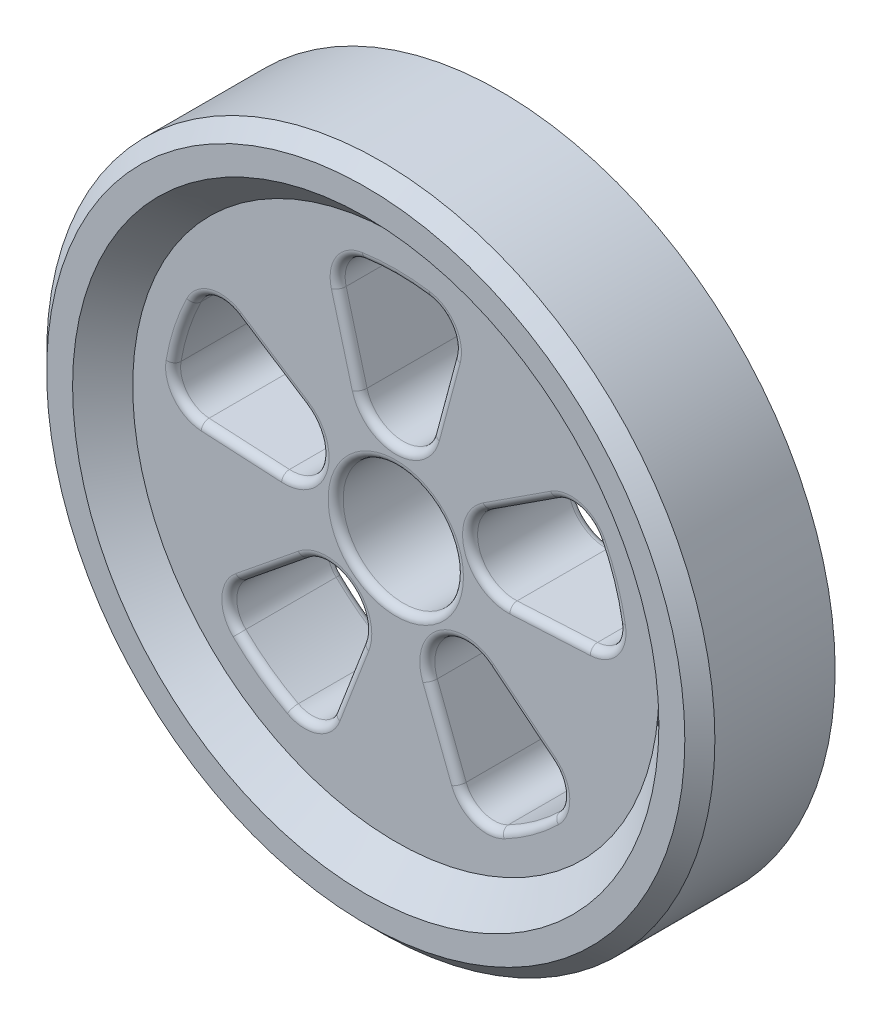
SolidWorks part; units mm, degrees
ref_plane "Front Plane" through (0, 0, 0) normal (0, 0, 1) x (1, 0, 0)
ref_plane "Top Plane" through (0, 0, 0) normal (0, 1, 0) x (1, 0, 0)
ref_plane "Right Plane" through (0, 0, 0) normal (1, 0, 0) x (0, 0, -1)
sketch "Sketch1" plane through (0, 0, 0) normal (0, 0, 1) x (1, 0, 0)
  line L0 (0, 0) -> (0, 10) construction
  line L1 (0, 0) -> (-7.0711, 7.0711) construction
  line L2 (2.4148, 7.1746) -> (3.8008, 12.3473)
  line L3 (-2.4148, 7.1746) -> (-3.8008, 12.3473)
  line L4 (6.0772, 4.5137) -> (10.5685, 7.4303)
  line L5 (7.5696, -0.0796) -> (12.9175, 0.2007)
  line L6 (6.1707, -4.385) -> (10.3325, -7.7551)
  line L7 (2.2635, -7.2237) -> (4.1826, -12.2233)
  line L8 (-2.2635, -7.2237) -> (-4.1826, -12.2233)
  line L9 (-6.1707, -4.385) -> (-10.3325, -7.7551)
  line L10 (-7.5696, -0.0796) -> (-12.9175, 0.2007)
  line L11 (-6.0772, 4.5137) -> (-10.5685, 7.4303)
  circle A1 centre (0, 0) radius 4
  circle A2 centre (0, 0) radius 10 construction
  circle A3 centre (0, 0) radius 22.225
  arc A4 (2.4148, 7.1746) -> (-2.4148, 7.1746) centre (0, 7.8216) cw
  arc A5 (52.7898, 163.2337) -> (51.4473, 165.6465) centre (50.8541, 163.7365) ccw
  arc A6 (2.1565, 14.8442) -> (-2.1565, 14.8442) centre (0, 0) ccw
  arc A7 (3.8008, 12.3473) -> (2.1565, 14.8442) centre (1.869, 12.8649) ccw
  arc A8 (-3.8008, 12.3473) -> (-2.1565, 14.8442) centre (-1.869, 12.8649) cw
  arc A9 (14.784, 2.5361) -> (13.4512, 6.6381) centre (0, 0) ccw
  arc A10 (12.9175, 0.2007) -> (14.784, 2.5361) centre (12.8128, 2.198) ccw
  arc A11 (10.5685, 7.4303) -> (13.4512, 6.6381) centre (11.6577, 5.753) cw
  arc A12 (7.5696, -0.0796) -> (6.0772, 4.5137) centre (7.4388, 2.417) cw
  arc A13 (6.9805, -13.2768) -> (10.4699, -10.7416) centre (0, 0) ccw
  arc A14 (4.1826, -12.2233) -> (6.9805, -13.2768) centre (6.0498, -11.5065) ccw
  arc A15 (10.3325, -7.7551) -> (10.4699, -10.7416) centre (9.0739, -9.3094) cw
  arc A16 (2.2635, -7.2237) -> (6.1707, -4.385) centre (4.5974, -6.3278) cw
  arc A17 (-10.4699, -10.7416) -> (-6.9805, -13.2768) centre (0, 0) ccw
  arc A18 (-10.3325, -7.7551) -> (-10.4699, -10.7416) centre (-9.0739, -9.3094) ccw
  arc A19 (-4.1826, -12.2233) -> (-6.9805, -13.2768) centre (-6.0498, -11.5065) cw
  arc A20 (-6.1707, -4.385) -> (-2.2635, -7.2237) centre (-4.5974, -6.3278) cw
  arc A21 (-13.4512, 6.6381) -> (-14.784, 2.5361) centre (0, 0) ccw
  arc A22 (-10.5685, 7.4303) -> (-13.4512, 6.6381) centre (-11.6577, 5.753) ccw
  arc A23 (-12.9175, 0.2007) -> (-14.784, 2.5361) centre (-12.8128, 2.198) cw
  arc A24 (-6.0772, 4.5137) -> (-7.5696, -0.0796) centre (-7.4388, 2.417) cw
  point P14 (53.2668, 165.0703)
  point P18 (4.3397, 14.3585)
  point P22 (-4.3397, 14.3585)
  point P61 (0, 0)
  dimension "D1" = 20
  dimension "D2" = 44.45
  dimension "D3" = 8
  dimension "D5" = 2
  dimension "D6" = 5
  dimension "D8" = 2.5
  dimension "D9" = 15
  dimension "D4" = 45
  dimension "D10" = 15
extrude "Boss-Extrude1" add sketch "Sketch1" along normal mid plane 9 contours A3 A1 L3 A8 A6 A7 L2 A4 L5 A12 L4 A11 A9 A10 L7 A16 L6 A15 A13 A14 L9 A20 L8 A19 A17 A18 L11 A24 L10 A23 A21 A22 region at (-21.5964, 0, 0)
sketch "Sketch2" plane through (0, 0, 4.5) normal (0, 0, 1) x (1, 0, 0)
  circle A0 centre (0, 0) radius 17.5
  dimension "D1" = 35
extrude "Cut-Extrude1" cut sketch "Sketch2" against normal blind 2
chamfer "Chamfer1" distance 2 angle 45 1 edges at (17.5, 0, 4.5)
chamfer "Chamfer2" distance 1 angle 45 1 edges at (22.225, 0, 4.5)
fillet "Fillet4" radius 0.5 62 edges at (-5.0612, 1.6445, -4.5) (-10.2436, 0.0606, -4.5) (-14.3752, 0.9493, -4.5) (-14.2658, 4.6353, -4.5) (-12.1877, 7.6815, -4.5) (-8.3228, 5.972, -4.5) (-3.128, -4.3053, -4.5) (-3.223, -9.7235, -4.5) (-5.345, -13.3782, -4.5) (-8.8168, -12.1353, -4.5) (-11.0718, -9.2175, -4.5) (-8.2516, -6.07, -4.5) (3.128, -4.3053, -4.5) (8.2516, -6.07, -4.5) (11.0718, -9.2175, -4.5) (8.8168, -12.1353, -4.5) (5.345, -13.3782, -4.5) (3.223, -9.7235, -4.5) (5.0612, 1.6445, -4.5) (8.3228, 5.972, -4.5) (12.1877, 7.6815, -4.5) (14.2658, 4.6353, -4.5) (10.2436, 0.0606, -4.5) (-3.5393, 13.9649, -4.5) (0, 15, -4.5) (3.5393, 13.9649, -4.5) (3.1078, 9.7609, -4.5) (0, 5.3216, -4.5) (-3.1078, 9.7609, -4.5) (4, 0, -4.5) (14.3752, 0.9493, -4.5) (0, 5.3216, 2.5) (3.1078, 9.7609, 2.5) (3.5393, 13.9649, 2.5) (0, 15, 2.5) (-3.5393, 13.9649, 2.5) (-3.1078, 9.7609, 2.5) (4, 0, 2.5) (-8.3228, 5.972, 2.5) (-12.1877, 7.6815, 2.5) (-14.2658, 4.6353, 2.5) (-10.2436, 0.0606, 2.5) (-5.0612, 1.6445, 2.5) (10.2436, 0.0606, 2.5) (14.3752, 0.9493, 2.5) (14.2658, 4.6353, 2.5) (12.1877, 7.6815, 2.5) (8.3228, 5.972, 2.5) (5.0612, 1.6445, 2.5) (3.223, -9.7235, 2.5) (5.345, -13.3782, 2.5) (8.8168, -12.1353, 2.5) (11.0718, -9.2175, 2.5) (8.2516, -6.07, 2.5) (3.128, -4.3053, 2.5) (-8.2516, -6.07, 2.5) (-11.0718, -9.2175, 2.5) (-8.8168, -12.1353, 2.5) (-5.345, -13.3782, 2.5) (-3.223, -9.7235, 2.5) (-3.128, -4.3053, 2.5) (-14.3752, 0.9493, 2.5)
